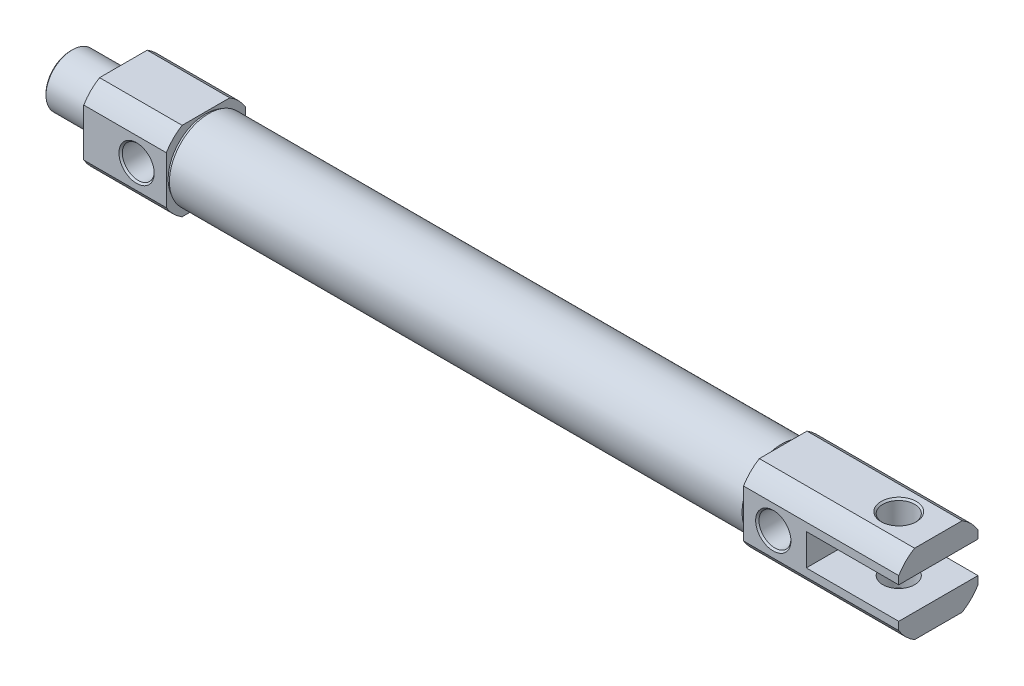
SolidWorks part; units mm, degrees
ref_plane "Front Plane" through (0, 0, 0) normal (0, 0, 1) x (1, 0, 0)
ref_plane "Top Plane" through (0, 0, 0) normal (0, 1, 0) x (1, 0, 0)
ref_plane "Right Plane" through (0, 0, 0) normal (1, 0, 0) x (0, 0, -1)
sketch "Sketch1" plane through (0, 0, 0) normal (1, 0, 0) x (0, 0, -1)
  circle A0 centre (0, 0) radius 5
  circle A1 centre (0, 0) radius 5.97
  dimension "D1" = 10
  dimension "D2" = 11.94
extrude "Boss-Extrude1" add sketch "Sketch1" along normal mid plane 80.4 contours A0 region at (0, 0, 0)
extrude "Boss-Extrude2" add sketch "Sketch1<3>" along normal mid plane 87.4
sketch "Sketch1<3>" plane through (0, 0, 0) normal (1, 0, 0) x (0, 0, -1) same geometry as "Sketch1"
chamfer "Chamfer1" distance 0.254 angle 60 1 edges at (43.7, 0, -5.97) first distance on face at (43.7, 0, -5.97)
chamfer "Chamfer2" distance 0.254 angle 60 1 edges at (-43.7, 0, -5.97) first distance on face at (-43.7, 0, -5.97)
sketch "Sketch2" plane through (43.7, 0, 0) normal (1, 0, 0) x (0, 0, -1)
  line L1 (6, -6) -> (-6, -6)
  line L2 (6, -6) -> (6, 6)
  line L3 (6, 6) -> (-6, 6)
  line L4 (-6, -6) -> (-6, 6)
  line L5 (6, -6) -> (-6, 6) construction
  line L6 (6, 6) -> (-6, -6) construction
  circle A0 centre (0, 0) radius 7
  point P0 (0, 0)
  dimension "D3" = 14
  dimension "D1" = 12
  dimension "D2" = 12
sketch "Sketch3" plane through (43.7, 0, 0) normal (1, 0, 0) x (0, 0, -1)
  line L0 (-6, 3.6055) -> (-6, -3.6055)
  line L1 (6, 3.6055) -> (6, -3.6055)
  line L2 (-3.6055, 6) -> (3.6055, 6)
  line L3 (-3.6055, -6) -> (3.6055, -6)
  line L4 (6, -6) -> (6, 6) construction
  line L5 (6, 6) -> (-6, 6) construction
  line L6 (-6, -6) -> (-6, 6) construction
  line L7 (6, -6) -> (-6, -6) construction
  arc A0 (-6, 3.6055) -> (-3.6055, 6) centre (0, 0) cw
  arc A1 (6, 3.6055) -> (3.6055, 6) centre (0, 0) ccw
  arc A2 (6, -3.6055) -> (3.6055, -6) centre (0, 0) cw
  arc A3 (-6, -3.6055) -> (-3.6055, -6) centre (0, 0) ccw
  circle A4 centre (0, 0) radius 7 construction
extrude "Boss-Extrude3" add sketch "Sketch3" along normal blind 23.5001
sketch "Sketch5" plane through (0, 6, 0) normal (0, 1, 0) x (1, 0, 0)
  line L0 (67.2001, 3.6055) -> (67.2001, -3.6055) construction
  circle A0 centre (61.2001, 0) radius 2.415
  dimension "D2" = 4.8301
  dimension "D1" = 6
extrude "Cut-Extrude2" cut sketch "Sketch5" against normal through all
sketch "Sketch6" plane through (0, 0, 6) normal (0, 0, 1) x (1, 0, 0)
  line L0 (67.2001, 3.6055) -> (67.2001, -3.6055) construction
  line L1 (53.2001, -2.39) -> (67.2001, -2.39)
  line L2 (53.2001, -2.39) -> (53.2001, 2.39)
  line L3 (53.2001, 2.39) -> (67.2001, 2.39)
  line L4 (67.2001, -2.39) -> (67.2001, 2.39)
  line L5 (53.2001, -2.39) -> (67.2001, 2.39) construction
  line L6 (53.2001, 2.39) -> (67.2001, -2.39) construction
  point P0 (60.2001, 0)
  dimension "D1" = 14
  dimension "D2" = 4.78
extrude "Cut-Extrude3" cut sketch "Sketch6" against normal through all
extrude "Boss-Extrude4" add sketch "Sketch3<2>" against normal blind 12.5001 from surface starting at face at (-43.7, 0, -5.716)
sketch "Sketch3<2>" plane through (43.7, 0, 0) normal (1, 0, 0) x (0, 0, -1) same geometry as "Sketch3"
sketch "Sketch4" plane through (0, 0, 6) normal (0, 0, 1) x (1, 0, 0)
  line L0 (43.7, 3.6055) -> (43.7, -3.6055) construction
  line L1 (-43.7, 3.6055) -> (-43.7, -3.6055) construction
  circle A0 centre (48.2001, 0) radius 2.415
  circle A1 centre (-48.2001, 0) radius 2.415
  dimension "D2" = 4.8301
  dimension "D1" = 4.5001
  dimension "D3" = 4.5001
extrude "Cut-Extrude4" cut sketch "Sketch4" against normal blind 6
sketch "Sketch8" plane through (-56.2001, 0, 0) normal (-1, 0, 0) x (0, 0, 1)
  circle A0 centre (0, 0) radius 3.9688
  circle A1 centre (0, 0) radius 2.1827
  dimension "D1" = 4.3655
  dimension "D2" = 7.9375
extrude "Boss-Extrude5" add sketch "Sketch8" along normal blind 8
chamfer "Chamfer5" distance 0.254 angle 45 6 edges at (61.2001, -6, 2.415) (61.2001, 6, 2.415) (50.6151, 0, 6) (-45.7851, 0, 6) (-64.2001, 0, 3.9688) (-64.2001, 0, 2.1827)
equation "\"D2@Sketch2\"=\"D1@Sketch2\""
